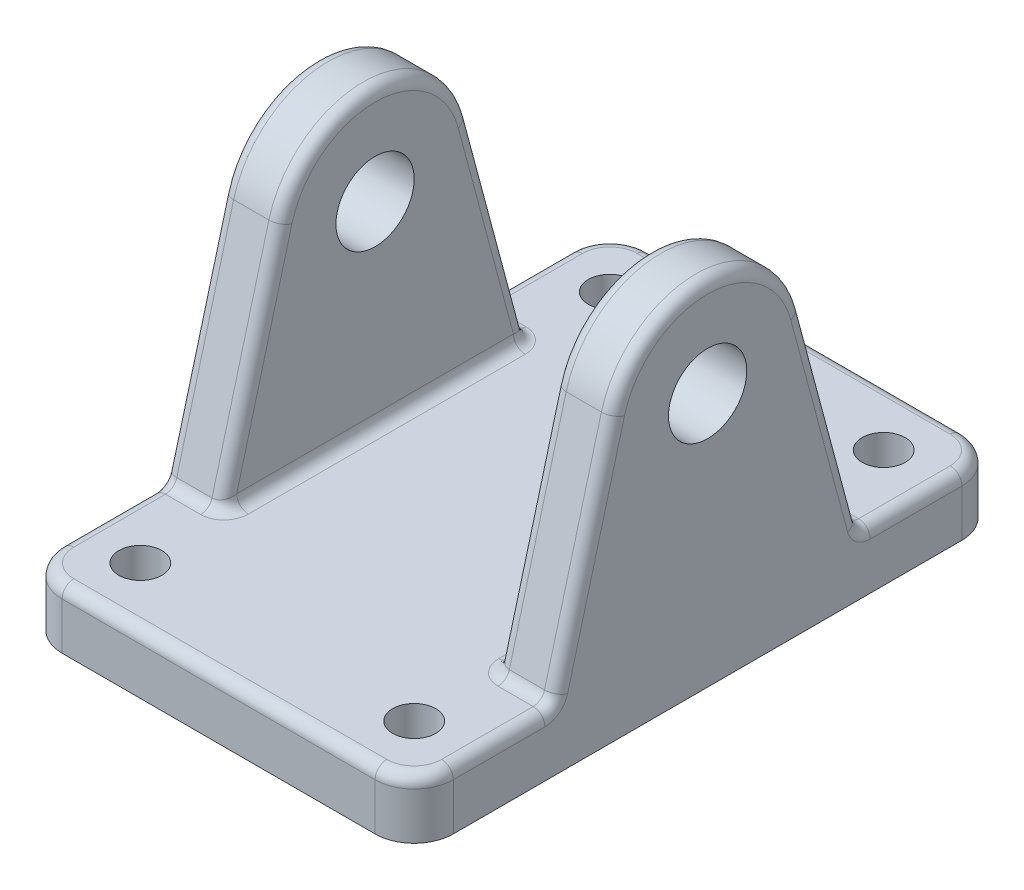
SolidWorks part; units mm, degrees
ref_plane "Front Plane" through (0, 0, 0) normal (0, 0, 1) x (1, 0, 0)
ref_plane "Top Plane" through (0, 0, 0) normal (0, 1, 0) x (1, 0, 0)
ref_plane "Right Plane" through (0, 0, 0) normal (1, 0, 0) x (0, 0, -1)
sketch "Sketch1" plane through (0, 0, 0) normal (0, 1, 0) x (1, 0, 0)
  line L1 (-50, -75) -> (50, -75)
  line L2 (-50, -75) -> (-50, 75)
  line L3 (-50, 75) -> (50, 75)
  line L4 (50, -75) -> (50, 75)
  line L5 (-50, -75) -> (50, 75) construction
  line L6 (-50, 75) -> (50, -75) construction
  point P0 (0, 0)
  dimension "D1" = 100
  dimension "D2" = 150
extrude "Base" add sketch "Sketch1" along normal blind 15
sketch "Sketch3" plane through (-50, 0, 0) normal (-1, 0, 0) x (0, 0, 1)
  line L0 (-39.2794, 15) -> (-24.1481, 71.4705)
  line L1 (-75, 15) -> (75, 15) construction
  line L2 (24.1481, 71.4705) -> (39.2794, 15)
  line L3 (0, 65) -> (0, 0) construction
  arc A0 (-24.1481, 71.4705) -> (24.1481, 71.4705) centre (0, 65) cw
  circle A1 centre (0, 65) radius 10
  line M4 (75, 15) -> (-75, 15)
  dimension "D3" = 25
  dimension "D4" = 50
  dimension "D5" = 20
  dimension "D1" = 75
  dimension "D2" = 75
extrude "Side flange" add sketch "Sketch3" against normal blind 15 contours A1 L2 A0 L0 M4 region at (-50, 45.5036, 0)
mirror "Mirror1" about plane through (0, 0, 0) normal (1, 0, 0) of "Side flange"
fillet "Fillet3" radius 10 4 edges at (-50, 7.5, 75) (50, 7.5, 75) (-50, 7.5, -75) (50, 7.5, -75)
hole_wizard "M10 Clearance Hole3" positions "Sketch8" profile "Sketch9" hole size "M10" standard "ANSI Metric" end condition through all
sketch "Sketch8" plane through (0, 15, 0) normal (0, 1, 0) x (1, 0, 0)
  line L1 (35, -60) -> (-35, -60)
  line L2 (35, -60) -> (35, 60)
  line L3 (35, 60) -> (-35, 60)
  line L4 (-35, -60) -> (-35, 60)
  line L5 (35, -60) -> (-35, 60) construction
  line L6 (35, 60) -> (-35, -60) construction
  line L7 (-50, 65) -> (-50, 39.2794) construction
  line L8 (40, 75) -> (-40, 75) construction
  point P0 (-35, 60)
  point P2 (35, 60)
  point P4 (35, -60)
  point P6 (-35, -60)
  point P221 (0, 0)
  point P222 (0, 0)
  point P223 (0, 0)
  dimension "D1" = 15
  dimension "D2" = 15
sketch "Sketch9" plane through (-35, 15, -60) normal (1, 0, 0) x (0, 0, 1)
  line L0 (0, 0) -> (0, 15)
  line L1 (0, 15) -> (5.5, 15)
  line L2 (5.5, 15) -> (5.5, 0)
  line L5 (5.5, 0) -> (0, 0)
  line L11 (0, -6.35) -> (0, 107.95) construction
  dimension "Thru Hole Dia." = 11
  dimension "Thru Hole Depth" = 15
fillet "Fillet6" radius 3 28 edges at (-50, 43.2352, -31.7138) (-42.5, 15, -39.2794) (-50, 90, 0) (42.5, 15, -39.2794) (-35, 15, 0) (42.5, 15, 39.2794) (-50, 43.2352, 31.7138) (-35, 43.2352, -31.7138) (-35, 90, 0) (50, 43.2352, -31.7138) (50, 90, 0) (35, 43.2352, -31.7138) (35, 90, 0) (50, 15, 52.1397) (47.0711, 15, 72.0711) (0, 15, 75) (-47.0711, 15, 72.0711) (50, 15, -52.1397) (47.0711, 15, -72.0711) (-50, 15, -52.1397) (-47.0711, 15, -72.0711) (-35, 43.2352, 31.7138) (50, 43.2352, 31.7138) (35, 43.2352, 31.7138) (35, 15, 0) (-42.5, 15, 39.2794) (-50, 15, 52.1397) (0, 15, -75)
